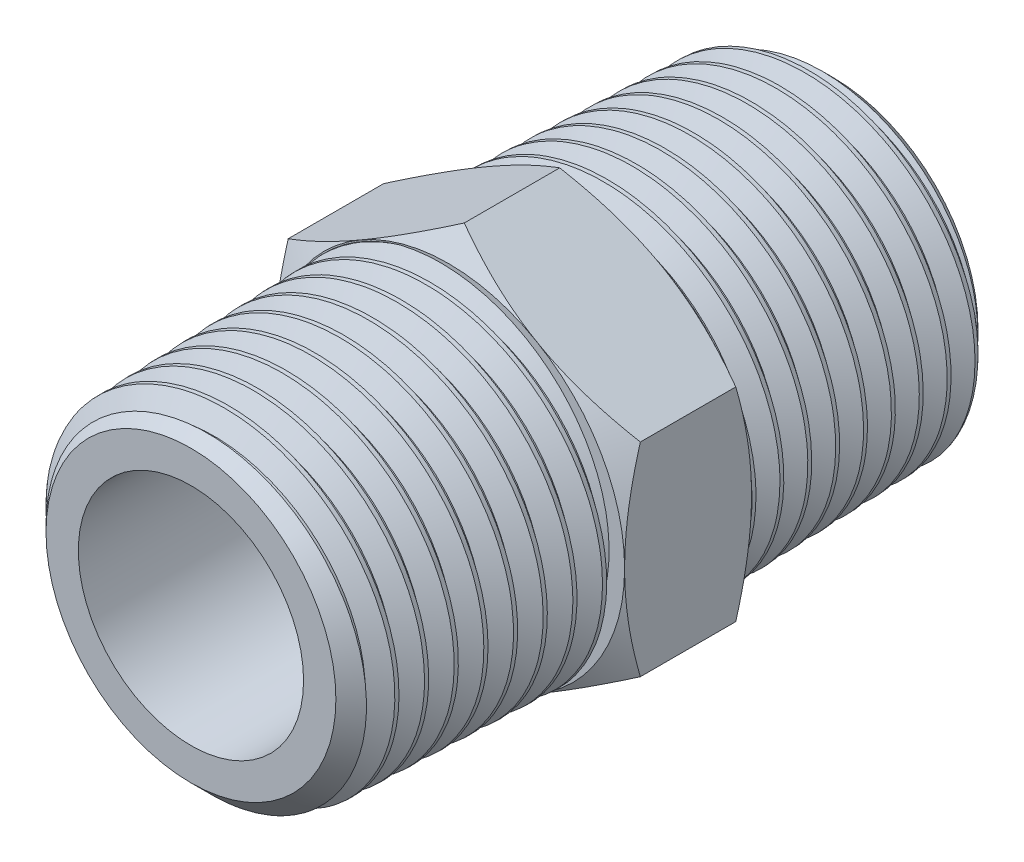
SolidWorks part; units mm, degrees
ref_plane "Front Plane" through (0, 0, 0) normal (0, 0, 1) x (1, 0, 0)
ref_plane "Top Plane" through (0, 0, 0) normal (0, 1, 0) x (1, 0, 0)
ref_plane "Right Plane" through (0, 0, 0) normal (1, 0, 0) x (0, 0, -1)
sketch "Sketch1" plane through (0, 0, 0) normal (1, 0, 0) x (0, 0, -1)
  line L0 (-3.1115, 8.636) -> (-3.1115, -8.636) construction
  line L1 (15.748, 0) -> (-15.748, 0) construction
  line L2 (15.748, 8.5725) -> (15.748, -8.5725) construction
  line L3 (0, 5.5245) -> (0, -5.5245) construction
  line L4 (-15.748, -8.5725) -> (-15.748, 8.5725) construction
  line L7 (-15.748, 8.5725) -> (-14.3369, 8.5725) construction
  line L8 (3.1115, 8.636) -> (3.1115, -8.636) construction
  point P2 (3.1115, 0)
  point P14 (-3.1115, 0)
sketch "Sketch2" plane through (0, 0, 0) normal (0, 0, 1) x (1, 0, 0)
  line L0 (0, 5.5245) -> (0, -5.5245) construction
  line L1 (0, 9.972) -> (-8.636, 4.986)
  line L2 (-8.636, 4.986) -> (-8.636, -4.986)
  line L3 (-8.636, -4.986) -> (0, -9.972)
  line L4 (0, -9.972) -> (8.636, -4.986)
  line L5 (8.636, -4.986) -> (8.636, 4.986)
  line L6 (8.636, 4.986) -> (0, 9.972)
  circle A0 centre (0, 0) radius 8.636 construction
extrude "Boss-Extrude1" add sketch "Sketch2" along normal up to vertex (3.1115 mm away) and the other way up to vertex (3.1115 mm away) up to point (0, 0, 3.1115) other way up to point (0, 0, -3.1115)
sketch "Sketch3" plane through (0, 0, 3.1115) normal (0, 0, 1) x (1, 0, 0)
  circle A0 centre (0, 0) radius 8.5725
extrude "Boss-Extrude2" add sketch "Sketch3" along normal up to vertex (12.6365 mm away) draft 1.783 separate body up to point (0, 0, 15.748)
sketch "Sketch4" plane through (0, 0, 15.748) normal (0, 0, 1) x (1, 0, 0)
  circle A1 centre (0, 0) radius 8.1791
  circle A2 centre (0, 0) radius 8.1791
  point P1 (0, 8.1791)
  dimension "D1" = 0
curve "Helix/Spiral1"
sketch "Sketch5" plane through (0, 0, 0) normal (1, 0, 0) x (0, 0, -1)
  line L0 (-15.6598, 8.3318) -> (-17.0709, 8.3318) construction
  line L1 (-17.0709, 8.3318) -> (-16.3654, 7.1098) construction
  line L2 (-16.3654, 7.1098) -> (-15.6598, 8.3318) construction
  line L3 (-16.2772, 7.2625) -> (-16.4536, 7.2625) construction
  line L4 (-15.748, 8.1791) -> (-16.9827, 8.1791) construction
  line L5 (-16.3654, 7.1098) -> (-16.3654, 7.2625) construction
  line L6 (-16.3654, 8.1791) -> (-16.3654, 8.3318) construction
  line L7 (-16.3654, 7.1098) -> (-16.3654, -8.1598) construction
  line L8 (-17.0268, 8.2554) -> (-16.3654, 8.2554) construction
  line L9 (-17.0268, 8.2554) -> (-15.6598, 8.3318)
  line L10 (-17.0268, 8.2554) -> (-16.4536, 7.2625)
  line L11 (-16.4536, 7.2625) -> (-16.2772, 7.2625)
  line L12 (-16.2772, 7.2625) -> (-15.6598, 8.3318)
  line L13 (-16.3654, -8.1598) -> (-14.9549, -8.2038) construction
  line L14 (-14.9549, -8.2038) -> (-13.5445, -8.2477) construction
  line L15 (-13.5445, -8.2477) -> (-12.1341, -8.2916) construction
  line L16 (-12.1341, -8.2916) -> (-13.5445, -8.2477) construction
  line L17 (-15.748, -8.1791) -> (-3.1115, -8.5725) construction
  dimension "D1" = 1.4111
  dimension "D2" = 0.1764
sweep "Cut-Sweep1" cut profiles "Sketch5" path "Helix/Spiral1"
sketch "Sketch6" plane through (0, 0, 15.748) normal (0, 0, 1) x (1, 0, 0)
  circle A0 centre (0, 0) radius 7.1098
extrude "Cut-Extrude1" cut sketch "Sketch6" against normal through all draft 45 flip side to cut
ref_axis "Axis1" through (0, 7.0574, 0) along (0, -1, 0)
pattern_circular "CirPattern1" count 2 over 360 about axis through (0, 7.0574, 0) along (0, -1, 0) of bodies 125 121
combine bodies "Combine1" operation type add bodies to combine 119 122 125
sketch "Sketch7" plane through (0, 0, 0) normal (1, 0, 0) x (0, 0, -1)
  line L0 (-3.1115, 8.636) -> (-3.1115, 9.972)
  line L1 (-15.748, 0) -> (15.748, 0)
  line L2 (-15.748, 0) -> (-15.748, 5.5245)
  line L3 (-15.748, 5.5245) -> (15.748, 5.5245)
  line L4 (15.748, 0) -> (15.748, 5.5245)
  line L5 (-3.1115, 9.972) -> (-2.3402, 9.972)
  line L6 (3.1115, 9.972) -> (3.1115, 8.636)
  line L7 (3.1115, 8.636) -> (2.3402, 9.972)
  line L8 (-3.1115, 9.972) -> (3.1115, 9.972) construction
  line L9 (-2.3402, 9.972) -> (-3.1115, 8.636)
  line L10 (2.3402, 9.972) -> (3.1115, 9.972)
  dimension "D1" = 30
revolve "Cut-Revolve1" cut sketch "Sketch7" angle 360 mid plane about L1
equation "\"D4@Helix/Spiral1\" = \"Pitch@Sketch1\""
equation "\"D3@Helix/Spiral1\" = \"Pitch@Sketch1\" + \"Thread Length@Sketch1\""
equation "\"D1@Sketch5\" = \"D4@Helix/Spiral1\""
equation "\"D2@Sketch5\" = \"D1@Sketch5\" / 8"
